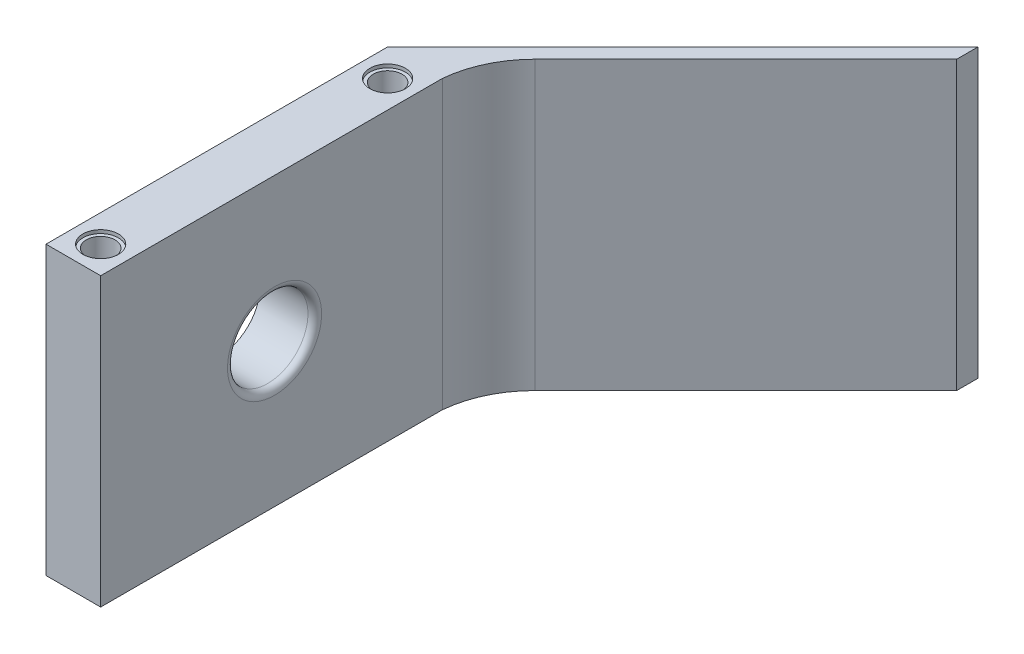
SolidWorks part; units mm, degrees
ref_plane "Front Plane" through (0, 0, 0) normal (0, 0, 1) x (1, 0, 0)
ref_plane "Top Plane" through (0, 0, 0) normal (0, 1, 0) x (1, 0, 0)
ref_plane "Right Plane" through (0, 0, 0) normal (1, 0, 0) x (0, 0, -1)
sketch "Sketch1" plane through (0, 0, 0) normal (0, 1, 0) x (1, 0, 0)
  line L1 (-10.223, 36.3848) -> (14.777, 36.3848)
  line L2 (-10.223, 36.3848) -> (-10.223, -13.6152)
  line L3 (-10.223, -13.6152) -> (14.777, -13.6152)
  line L4 (14.777, 36.3848) -> (14.777, -13.6152)
  circle A0 centre (1.277, 11.3848) radius 3.4
  dimension "D3" = 6.8
  dimension "D1" = 50
  dimension "D2" = 25
  dimension "D4" = 13.5
  dimension "D5" = 25
extrude "Boss-Extrude1" add sketch "Sketch1" along normal blind 3
sketch "Sketch2" plane through (-10.223, 0, 0) normal (-1, 0, 0) x (0, 0, 1)
  line L0 (18.15, 0) -> (-18.15, 0) construction
  line L1 (-36.3848, 3) -> (13.6152, 3)
  line L2 (-36.3848, 3) -> (-36.3848, 0)
  line L3 (-36.3848, 0) -> (13.6152, 0)
  line L4 (13.6152, 3) -> (13.6152, 0)
  line L5 (13.6152, 3) -> (13.6152, 0) construction
extrude "Boss-Extrude2" add sketch "Sketch2" along normal blind 8
sketch "Sketch3" plane through (0, 0, 0) normal (0, -1, 0) x (1, 0, 0)
  line L0 (-18.223, 13.6152) -> (14.777, 13.6152) construction
  line L1 (-18.223, -36.3848) -> (-10.223, -36.3848)
  line L2 (-18.223, -36.3848) -> (-18.223, 13.6152)
  line L3 (-18.223, 13.6152) -> (-10.223, 13.6152)
  line L4 (-10.223, -36.3848) -> (-10.223, 13.6152)
  dimension "D1" = 8
extrude "Boss-Extrude3" add sketch "Sketch3" along normal blind 42
sketch "Sketch4" plane through (0, 3, 0) normal (0, 1, 0) x (1, 0, 0)
  line L0 (-18.223, -13.6152) -> (-18.223, 36.3848) construction
  line L1 (14.777, 36.3848) -> (-18.223, 36.3848) construction
  line L2 (-18.223, -13.6152) -> (14.777, -13.6152) construction
  circle A0 centre (-14.223, 32.3848) radius 2.65
  circle A1 centre (-14.223, -9.6152) radius 2.65
  dimension "D2" = 5.3
  dimension "D4" = 5.3
  dimension "D5" = 4
  dimension "D6" = 4
  dimension "D1" = 4
  dimension "D3" = 4
extrude "Cut-Extrude1" cut sketch "Sketch4" against normal blind 0.5
ref_plane "Plane1" through (0, -19.5, 0) normal (0, 1, 0) x (1, 0, 0)
mirror "Mirror1" about plane through (0, -19.5, 0) normal (0, 1, 0) of "Cut-Extrude1"
sketch "Sketch5" plane through (-18.223, 0, 0) normal (-1, 0, 0) x (0, 0, 1)
  line L0 (18.15, 0) -> (-18.15, 0) construction
  line L1 (-6.9117, -24.2293) -> (-6.5773, -18.3498) construction
  line L2 (-6.5773, -18.3498) -> (-11.502, -15.1205) construction
  line L3 (-11.502, -15.1205) -> (-16.7609, -17.7707) construction
  line L4 (-16.7609, -17.7707) -> (-17.0952, -23.6502) construction
  line L5 (-17.0952, -23.6502) -> (-12.1706, -26.8795) construction
  line L6 (-12.1706, -26.8795) -> (-6.9117, -24.2293) construction
  circle A0 centre (-11.8363, -21) radius 5.1 construction
  circle A1 centre (-11.8363, -21) radius 5.889
  dimension "D1" = 21
  dimension "D2" = 10.2
extrude "Cut-Extrude2" cut sketch "Sketch5" against normal blind 9
fillet "Fillet2" radius 1 1 edges at (-10.223, -21, -5.9473)
ref_plane "Plane2" through (-1.723, 0, 0) normal (-1, 0, 0) x (0, 0, 1)
mirror "Mirror2" about plane through (-1.723, 0, 0) normal (-1, 0, 0) of "Cut-Extrude1"
sketch "Sketch6" plane through (0, 3, 0) normal (0, 1, 0) x (1, 0, 0)
  line L0 (1.277, 14.7848) -> (1.277, 7.9848) construction
  line L1 (14.777, -13.6152) -> (14.777, 36.3848) construction
  line L2 (14.777, 16.9444) -> (14.777, 5.8251)
  circle A0 centre (1.277, 11.3848) radius 3.4 construction
  circle A1 centre (1.277, 11.3848) radius 3.1
  circle A2 centre (1.277, 11.3848) radius 12.6
  arc A3 (14.777, 16.9444) -> (14.777, 5.8251) centre (1.277, 11.3848) ccw
  line M9 (14.777, -13.6152) -> (14.777, 36.3848)
  dimension "D1" = 25.2
  dimension "D2" = 2
extrude "Boss-Extrude4" add sketch "Sketch6" along normal blind 2 contours A3 A2 M9
fillet "Fillet4" radius 1 1 edges at (14.777, 5, -11.3848)
sketch "Sketch8" plane through (0, 3, 0) normal (0, 1, 0) x (1, 0, 0)
  line L0 (4.677, 11.3848) -> (-2.123, 11.3848) construction
  circle A0 centre (1.277, 11.3848) radius 3.4 construction
  circle A1 centre (1.277, 19.8848) radius 1.5898
  circle A2 centre (1.277, 2.8848) radius 1.7774
  point P9 (1.277, 11.3848)
  dimension "D1" = 8.5
  dimension "D2" = 8.5
extrude "Cut-Extrude3" cut sketch "Sketch8" against normal blind 10
sketch "Sketch9" plane through (0, 0, 13.6152) normal (0, 0, 1) x (1, 0, 0)
  line L1 (14.777, 0) -> (-34.2447, 0)
  line L2 (14.777, 0) -> (14.777, 20.9769)
  line L3 (14.777, 20.9769) -> (-34.2447, 20.9769)
  line L4 (-34.2447, 0) -> (-34.2447, 20.9769)
extrude "Cut-Extrude4" cut sketch "Sketch9" against normal through all
ref_plane "Plane3" through (0, 0, -11.3848) normal (0, 0, 1) x (1, 0, 0)
sketch "Sketch11" plane through (0, 0, 0) normal (0, 1, 0) x (1, 0, 0)
  circle A2 centre (-14.223, 32.3848) radius 2.1
  dimension "D1" = 4.2
extrude "Cut-Extrude5" cut sketch "Sketch11" against normal through all contours A2
mirror "Mirror3" about plane through (0, 0, -11.3848) normal (0, 0, 1) of "Cut-Extrude5"
sketch "Sketch14" plane through (0, 0, 0) normal (0, 1, 0) x (1, 0, 0)
  circle A0 centre (-14.223, -9.6152) radius 2.6
  dimension "D1" = 5.2
extrude "Cut-Extrude6" cut sketch "Sketch14" against normal blind 0.5
mirror "Mirror4" about plane through (0, 0, -11.3848) normal (0, 0, 1) of "Cut-Extrude6"
sketch "Sketch15" plane through (0, 0, 0) normal (0, 1, 0) x (1, 0, 0)
  line L0 (-18.223, 36.3848) -> (-10.223, 36.3848) construction
  line L1 (24.977, 103.9918) -> (24.977, -151.6223) construction
  line L2 (-18.223, 36.3848) -> (24.977, 79.5848)
  line L3 (-15.1105, 36.3848) -> (24.977, 76.4722)
  line L4 (24.977, 76.4722) -> (24.977, 79.5848)
  line L5 (-15.1105, 36.3848) -> (-18.223, 36.3848)
  dimension "D1" = 45
extrude "Boss-Extrude5" add sketch "Sketch15" against normal up to surface (42 mm away) up to face at (-14.223, -42, -29.7348)
fillet "Fillet5" radius 15 1 edges at (-15.1105, -21, -36.3848)
